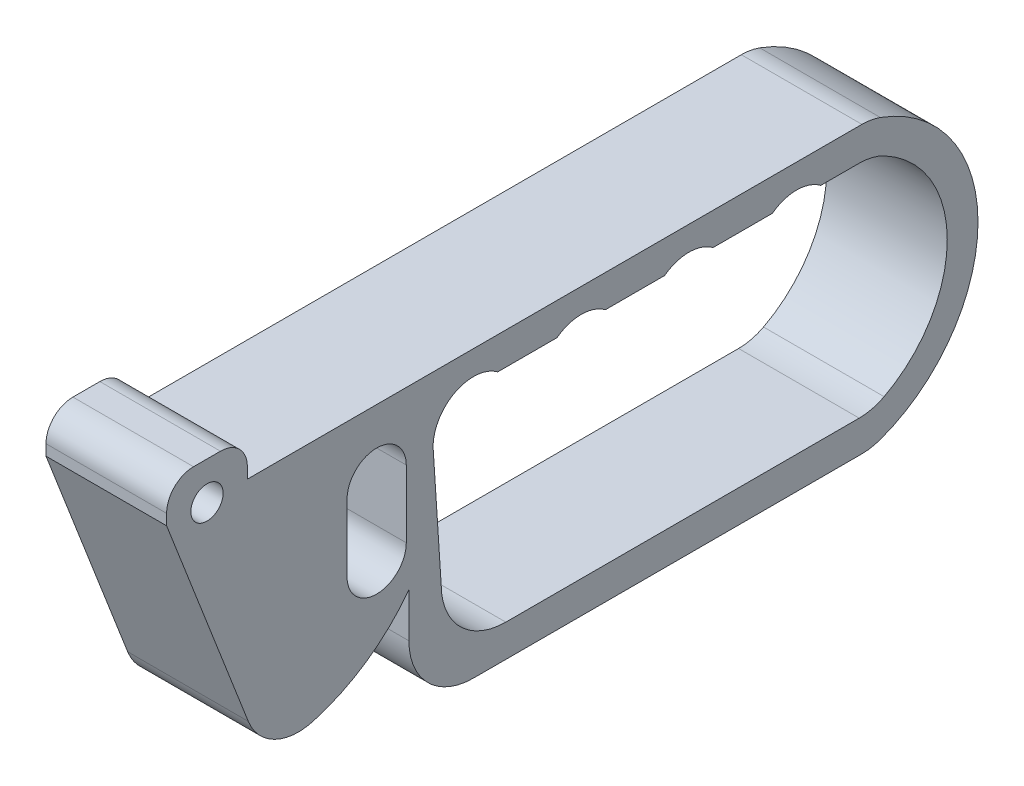
SolidWorks part; units mm, degrees
ref_plane "Front Plane" through (0, 0, 0) normal (0, 0, 1) x (1, 0, 0)
ref_plane "Top Plane" through (0, 0, 0) normal (0, 1, 0) x (1, 0, 0)
ref_plane "Right Plane" through (0, 0, 0) normal (1, 0, 0) x (0, 0, -1)
sketch "Sketch2" plane through (0, 0, 0) normal (1, 0, 0) x (0, 0, -1)
  line L0 (32.85, -26.5) -> (32.85, 26.5) construction
  line L1 (-52.85, 26.5) -> (32.85, 26.5)
  line L2 (-52.85, 26.5) -> (-52.85, -14.5)
  line L3 (-40.85, -26.5) -> (32.85, -26.5)
  line L4 (52.85, 26.5) -> (52.85, -26.5) construction
  line L5 (-52.85, 26.5) -> (52.85, -26.5) construction
  line L6 (-52.85, -26.5) -> (52.85, 26.5) construction
  line L7 (32.85, 0) -> (52.85, 0) construction
  line L8 (32.85, 26.5) -> (52.85, 26.5) construction
  line L9 (32.85, 20.5) -> (-40.85, 20.5)
  line L10 (-46.85, 14.5) -> (-46.85, -8.5)
  line L11 (-34.85, -20.5) -> (32.85, -20.5)
  arc A0 (32.85, 26.5) -> (32.85, -26.5) centre (25.2938, 0) cw
  arc A1 (-52.85, -14.5) -> (-40.85, -26.5) centre (-40.85, -14.5) ccw
  arc A2 (32.85, 20.5) -> (32.85, -20.5) centre (25.2938, 0) cw
  arc A3 (-40.85, 20.5) -> (-46.85, 14.5) centre (-40.85, 14.5) ccw
  arc A4 (-46.85, -8.5) -> (-34.85, -20.5) centre (-34.85, -8.5) ccw
  point P0 (0, 0)
  dimension "D4" = 12
  dimension "D7" = 0
  dimension "D9" = 6
  dimension "D10" = 12
  dimension "D1" = 53
  dimension "D2" = 105.7
  dimension "D3" = 20
  dimension "D5" = 6
  dimension "D6" = 6
  dimension "D8" = 6
extrude "Boss-Extrude1" add sketch "Sketch2" along normal blind 11.2 and the other way blind 11.2
sketch "Sketch3" plane through (0, 0, 0) normal (1, 0, 0) x (0, 0, -1)
  line L1 (-40.85, 14.5) -> (39.15, 14.5) construction
  arc A0 (-40.85, 20.5) -> (-46.85, 14.5) centre (-40.85, 14.5) ccw construction
  arc A1 (-40.85, 20.5) -> (-46.85, 14.5) centre (-40.85, 14.5) ccw construction
  circle A3 centre (-40.85, 14.5) radius 7.5
  circle A4 centre (-20.85, 14.5) radius 7.5
  circle A5 centre (-0.85, 14.5) radius 7.5
  circle A6 centre (19.15, 14.5) radius 7.5
  dimension "D3" = 15
  dimension "D1" = 80
  dimension "D2" = 4
  dimension "D4" = 20
extrude "Cut-Extrude1" cut sketch "Sketch3" against normal up to surface and the other way up to surface up to face at (-11.2, 0.7929, 15.5227) other way up to face at (11.2, -3.3971, 12.6671)
fillet "Fillet1" radius 10 1 edges at (0, 20.5, -32.85)
sketch "Sketch4" plane through (0, 0, 0) normal (1, 0, 0) x (0, 0, -1)
  line L0 (-46.85, -8.5) -> (-48.3338, 14.0066)
  line L1 (-48.3338, 14.0066) -> (-46.85, 14.0066)
  line L2 (-46.85, 14.0066) -> (-46.85, -8.5)
  arc A0 (-36.35, 20.5) -> (-46.85, 10) centre (-40.85, 14.5) ccw construction
  arc A1 (-36.35, 20.5) -> (-46.85, 10) centre (-40.85, 14.5) ccw construction
  dimension "D1" = 1.4838
extrude "Cut-Extrude2" cut sketch "Sketch4" along normal up to surface and the other way up to surface up to face at (11.2, 11.5289, 4.9967) other way up to face at (-11.2, 11.5289, 4.9967)
fillet "Fillet2" radius 10 3 edges at (0, 26.5, -32.85) (0, -20.5, -32.85) (0, -26.5, -32.85)
sketch "Sketch5" plane through (0, 0, 0) normal (1, 0, 0) x (0, 0, -1)
  line L0 (-52.85, 26.5) -> (-52.85, -14.5) construction
  line L1 (-52.85, 26.5) -> (-52.85, -14.5) construction
  line L2 (-52.85, -14.5) -> (-50.0933, -19.8292) construction
  line L3 (-52.85, 26.5) -> (-97.85, 26.5) construction
  line L5 (-50.0933, -19.8292) -> (-97.85, -19.8292) construction
  line L6 (-97.85, 26.5) -> (-97.85, -19.8292) construction
  line L7 (-40.85, -26.5) -> (31.2914, -26.5) construction
  line L8 (-40.85, -26.5) -> (31.2914, -26.5) construction
  line L9 (-52.85, -6.3) -> (-52.85, 26.5)
  line L10 (-79.85, -19.8292) -> (-97.85, 26.5)
  line L11 (-82.85, 26.5) -> (-52.85, 26.5)
  line L12 (-97.85, 26.5) -> (-82.85, 26.5) construction
  line L13 (-97.85, 26.5) -> (-97.85, 28.5)
  line L14 (-92.85, 33.5) -> (-87.85, 33.5)
  line L15 (-82.85, 26.5) -> (-82.85, 28.5)
  arc A0 (-52.85, -6.3) -> (-79.85, -19.8292) centre (-79.85, 13.8771) cw
  arc A1 (-97.85, 28.5) -> (-92.85, 33.5) centre (-92.85, 28.5) cw
  arc A2 (-87.85, 33.5) -> (-82.85, 28.5) centre (-87.85, 28.5) cw
  point P15 (-97.85, 33.5)
  dimension "D7" = 5
  dimension "D1" = 27
  dimension "D2" = 20.2
  dimension "D3" = 30.2
  dimension "D4" = 45
  dimension "D5" = 7
  dimension "D6" = 30
  dimension "D8" = 6
extrude "Boss-Extrude2" add sketch "Sketch5" along normal up to surface (11.2 mm away) and the other way up to surface (11.2 mm away) up to face at (11.2, -2.4265, -0.1654) other way up to face at (-11.2, -2.4265, -0.1654)
fillet "Fillet3" radius 10 1 edges at (0, -19.8292, 79.85)
sketch "Sketch6" plane through (0, 0, 0) normal (1, 0, 0) x (0, 0, -1)
  line L0 (-58.8338, 14.0066) -> (-58.8338, 1.5066) construction
  line L1 (-53.3338, 14.0066) -> (-53.3338, 1.5066)
  line L2 (-64.3338, 14.0066) -> (-64.3338, 1.5066)
  line L3 (-58.8338, -3.9934) -> (-58.8338, 19.5066) construction
  line L4 (31.2914, 26.5) -> (-82.85, 26.5) construction
  line L5 (31.2914, 26.5) -> (-82.85, 26.5) construction
  line L6 (-53.3338, 14.0066) -> (-48.3338, 14.0066) construction
  arc A0 (-53.3338, 14.0066) -> (-64.3338, 14.0066) centre (-58.8338, 14.0066) ccw
  arc A1 (-64.3338, 1.5066) -> (-53.3338, 1.5066) centre (-58.8338, 1.5066) ccw
  arc A2 (-36.35, 20.5) -> (-48.3338, 14.0066) centre (-40.85, 14.5) ccw construction
  arc A3 (-36.35, 20.5) -> (-48.3338, 14.0066) centre (-40.85, 14.5) ccw construction
  point P2 (-58.8338, 7.7566)
  dimension "D1" = 11
  dimension "D2" = 23.5
  dimension "D3" = 5
extrude "Cut-Extrude3" cut sketch "Sketch6" along normal up to surface and the other way up to surface up to face at (11.2, 6.2937, 46.2932) other way up to face at (-11.2, 6.2937, 46.2932)
sketch "Sketch7" plane through (0, 0, 0) normal (1, 0, 0) x (0, 0, -1)
  line L0 (-90.35, 33.5) -> (-90.35, 26.5) construction
  line L1 (-87.85, 33.5) -> (-92.85, 33.5) construction
  circle A0 centre (-90.35, 26.5) radius 3
  dimension "D1" = 6
extrude "Cut-Extrude4" cut sketch "Sketch7" along normal up to surface and the other way up to surface up to face at (11.2, 6.2937, 46.2932) other way up to face at (-11.2, 9.5973, 2.2706)
